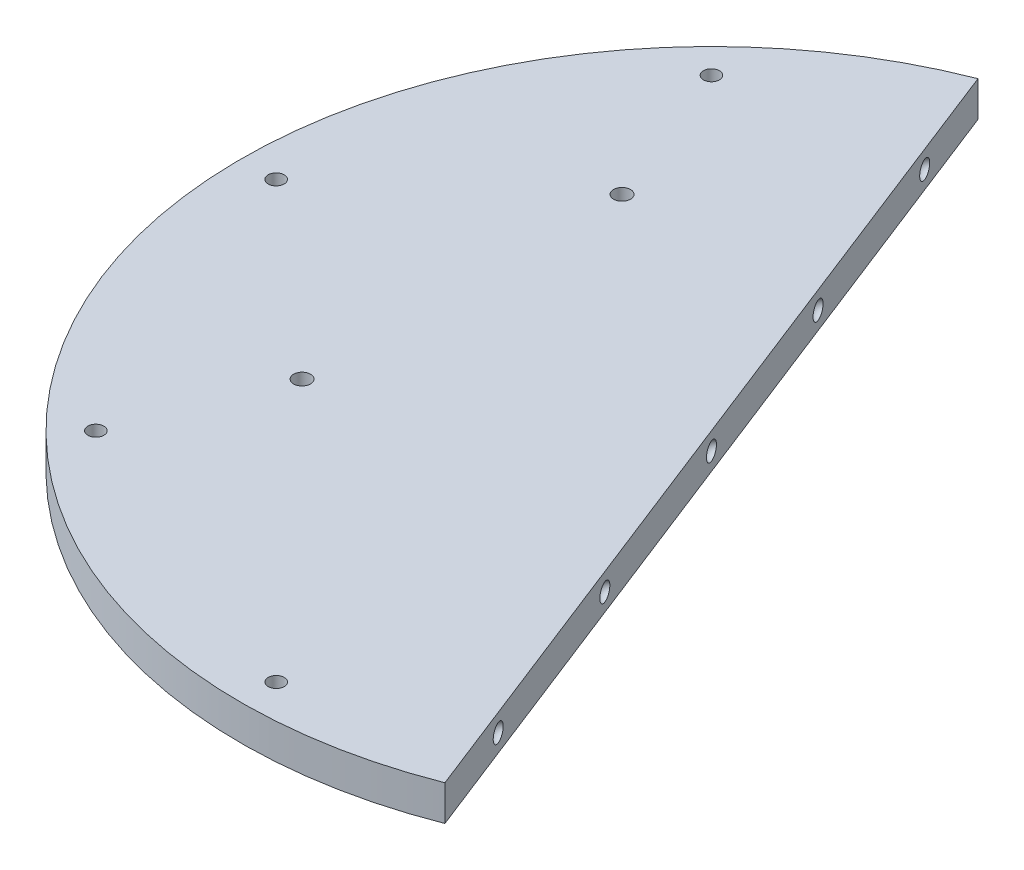
SolidWorks part; units mm, degrees
ref_plane "Front Plane" through (0, 0, 0) normal (0, 0, 1) x (1, 0, 0)
ref_plane "Top Plane" through (0, 0, 0) normal (0, 1, 0) x (1, 0, 0)
ref_plane "Right Plane" through (0, 0, 0) normal (1, 0, 0) x (0, 0, -1)
sketch "Sketch1" plane through (0, 0, 0) normal (0, 1, 0) x (1, 0, 0)
  circle A0 centre (0, 0) radius 100
  dimension "D1" = 200
extrude "Boss-Extrude1" add sketch "Sketch1" along normal blind 7.5
hole_wizard "CBORE for M3 SHCS1" positions "Sketch2" profile "Sketch3" counterbore size "M3" standard "ANSI Metric"
sketch "Sketch2" plane through (0, 0, 0) normal (0, -1, 0) x (-1, 0, 0)
  line L1 (0, -85) -> (0, -100) construction
  line L3 (0, 0) -> (0, -85) construction
  line L4 (0, 0) -> (0, 92.5) construction
  line L6 (0, 0) -> (92.5, 0) construction
  circle A0 centre (0, 0) radius 100 construction
  point P0 (0, -92.5)
  point P17 (-65.4074, -65.4074)
  point P18 (-92.5, 0)
  point P19 (-65.4074, 65.4074)
  point P20 (0, 92.5)
  point P21 (65.4074, 65.4074)
  point P22 (92.5, 0)
  point P23 (65.4074, -65.4074)
  dimension "D1" = 15
  dimension "D2" = 8
sketch "Sketch3" plane through (0, 0, 92.5) normal (1, 0, 0) x (0, 0, -1)
  line L0 (0, 0) -> (0, 8.5215)
  line L1 (0, 8.5215) -> (1.7, 7.5)
  line L2 (1.7, 7.5) -> (1.7, 3)
  line L3 (1.7, 3) -> (3.25, 3)
  line L4 (3.25, 3) -> (3.25, 0)
  line L5 (3.25, 0) -> (0, 0)
  line L10 (0, 8.5215) -> (-1.7, 7.5) construction
  line L11 (0, -6.35) -> (0, 107.95) construction
  dimension "Hole Dia." = 3.4
  dimension "Hole Depth" = 7.5
  dimension "C'Bore Dia." = 6.5
  dimension "C'Bore Depth" = 3
  dimension "Drill Angle" = 118
sketch "Sketch4" plane through (0, 0, 0) normal (0, 1, 0) x (1, 0, 0)
  line L0 (-53, -34) -> (-53, 34) construction
  line L1 (-53, 34) -> (53, 34) construction
  line L2 (53, 34) -> (53, -34) construction
  line L3 (53, -34) -> (-53, -34) construction
  line L4 (0, 34) -> (0, -34) construction
  point P8 (0, 0)
  dimension "D1" = 106
  dimension "D2" = 68
hole_wizard "CBORE for M3 SHCS2" positions "Sketch5" profile "Sketch6" counterbore size "M3" standard "ANSI Metric"
sketch "Sketch5" plane through (0, 0, 0) normal (0, -1, 0) x (-1, 0, 0)
  point P0 (-53, 34)
  point P3 (53, 34)
  point P6 (53, -34)
  point P9 (-53, -34)
sketch "Sketch6" plane through (53, 0, -34) normal (1, 0, 0) x (0, 0, -1)
  line L0 (0, 0) -> (0, 8.5815)
  line L1 (0, 8.5815) -> (1.8, 7.5)
  line L2 (1.8, 7.5) -> (1.8, 3)
  line L3 (1.8, 3) -> (3.25, 3)
  line L4 (3.25, 3) -> (3.25, 0)
  line L5 (3.25, 0) -> (0, 0)
  line L10 (0, 8.5815) -> (-1.8, 7.5) construction
  line L11 (0, -6.35) -> (0, 107.95) construction
  dimension "Hole Dia." = 3.6
  dimension "Hole Depth" = 7.5
  dimension "C'Bore Dia." = 6.5
  dimension "C'Bore Depth" = 3
  dimension "Drill Angle" = 118
sketch "Sketch8" plane through (0, 0, 0) normal (0, 1, 0) x (1, 0, 0)
  line L0 (-45.5873, 116.3907) -> (45.5873, -116.3907)
  point P2 (0, 0)
  dimension "D1" = 250
ref_plane "Plane1" through (0, 0, 0) normal (-0.9311, 0, 0.3647) x (0.3647, 0, 0.9311)
sketch "Sketch9" plane through (0, 0, 0) normal (-0.9311, 0, 0.3647) x (0.3647, 0, 0.9311)
  line L1 (-139.4421, 36.0587) -> (137.3978, 36.0587)
  line L2 (-139.4421, 36.0587) -> (-139.4421, -50.3959)
  line L3 (-139.4421, -50.3959) -> (137.3978, -50.3959)
  line L4 (137.3978, 36.0587) -> (137.3978, -50.3959)
extrude "Cut-Extrude1" cut sketch "Sketch9" against normal through all contours L3 L4 L1 L2
sketch "Sketch10" plane through (0, 0, 0) normal (-0.9311, 0, 0.3647) x (0.3647, 0, 0.9311)
  line L0 (-31.6583, 0) -> (31.6583, 0) construction
  line L3 (0, 3.75) -> (-40, 3.75) construction
  line L4 (0, 7.5) -> (0, 0) construction
  line L5 (-100, 7.5) -> (100, 7.5) construction
  circle A0 centre (0, 3.75) radius 1.875
  circle A1 centre (-40, 3.75) radius 1.875
  circle A2 centre (-80, 3.75) radius 1.875
  circle A3 centre (80, 3.75) radius 1.875
  circle A4 centre (40, 3.75) radius 1.875
  dimension "D1" = 3.75
  dimension "D2" = 3.75
  dimension "D3" = 0
  dimension "D5" = 40
  dimension "D4" = 3
extrude "Cut-Extrude2" cut sketch "Sketch10" along normal blind 1.875
fillet "Fillet1" radius 1.875 5 edges at (-30.2379, 3.75, -72.0604) (-15.65, 3.75, -34.8154) (26.7462, 3.75, 73.428) (12.1583, 3.75, 36.183) (-1.0621, 3.75, 2.4297)
